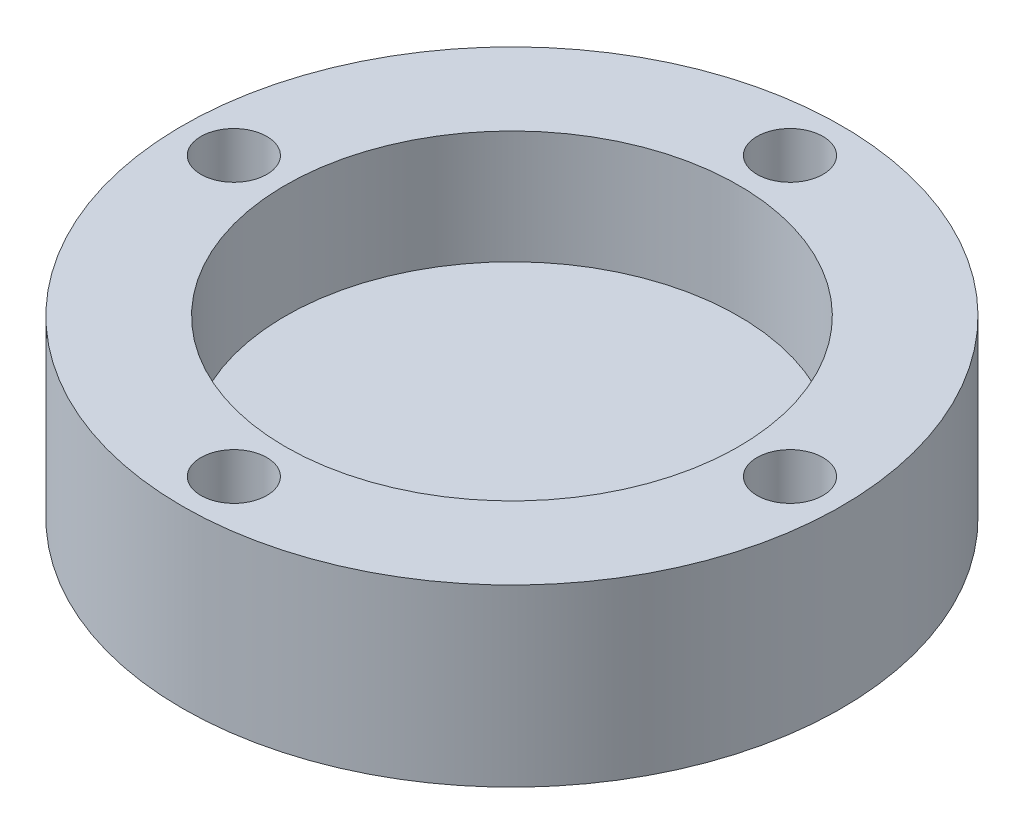
SolidWorks part; units mm, degrees
ref_plane "Front Plane" through (0, 0, 0) normal (0, 0, 1) x (1, 0, 0)
ref_plane "Top Plane" through (0, 0, 0) normal (0, 1, 0) x (1, 0, 0)
ref_plane "Right Plane" through (0, 0, 0) normal (1, 0, 0) x (0, 0, -1)
ref_axis "Axe1" through (0, 8.4, 0) along (0, -1, 0)
sketch "Esquisse1" plane through (0, 0, 0) normal (0, 0, 1) x (1, 0, 0)
  line L0 (11, 8.5) -> (11, 3)
  line L1 (11, 3) -> (0, 3)
  line L2 (0, 3) -> (0, 0)
  line L3 (0, 0) -> (16, 0)
  line L4 (16, 0) -> (16, 8.5)
  line L5 (11, 8.5) -> (16, 8.5)
  dimension "D1" = 5.5
  dimension "D2" = 3
  dimension "D3" = 11
  dimension "D4" = 5
revolve "MainRevolution" add sketch "Esquisse1" angle 360 about axis through (0, 8.4, 0) along (0, -1, 0)
sketch "Esquisse2" plane through (0, 8.5, 0) normal (0, 1, 0) x (1, 0, 0)
  circle A0 centre (13.5, 0) radius 1.6
  point P2 (0, 0)
  dimension "D1" = 3.2
  dimension "D2" = 13.5
extrude "FixingHole" cut sketch "Esquisse2" against normal through all
pattern_circular "FixingHoleRepetition" count 4 every 90 about axis through (0, 8.4, 0) along (0, -1, 0) of "FixingHole"
